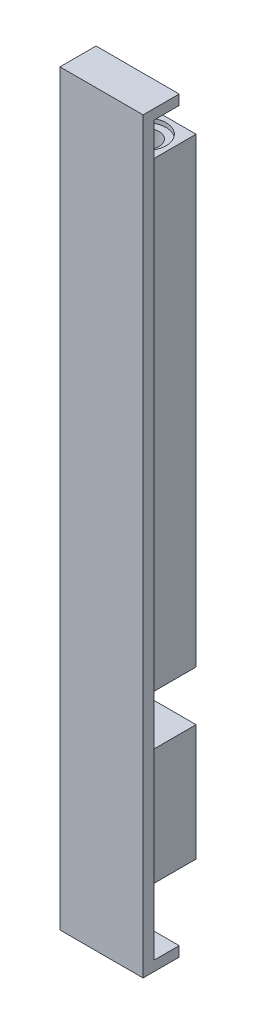
SolidWorks part; units mm, degrees
ref_plane "Front Plane" through (0, 0, 0) normal (0, 0, 1) x (1, 0, 0)
ref_plane "Top Plane" through (0, 0, 0) normal (0, 1, 0) x (1, 0, 0)
ref_plane "Right Plane" through (0, 0, 0) normal (1, 0, 0) x (0, 0, -1)
ref_plane "Plane7" through (0, -5, 0) normal (0, -1, 0) x (-1, 0, 0)
sketch "Sketch1" plane through (0, 0, 0) normal (0, 1, 0) x (1, 0, 0)
  circle A0 centre (0, 0) radius 37.5 construction
  dimension "D1" = 75
sketch "Sketch3" plane through (0, -5, 0) normal (0, -1, 0) x (1, 0, 0)
  line L0 (-3, 37.3798) -> (-3, 31.3798)
  line L1 (-3, 31.3798) -> (3, 31.3798)
  line L2 (3, 31.3798) -> (3, 37.3798)
  line L9 (0, 40.3758) -> (0, -39.6162) construction
  line L10 (0, -55) -> (0, 55) construction
  arc A0 (3, 37.3798) -> (-3, 37.3798) centre (0, 0) ccw
  circle A4 centre (0, 0) radius 37.5 construction
  dimension "D2" = 6
  dimension "D3" = 6
extrude "Boss-Extrude2" add sketch "Sketch3" along normal blind 75.5
sketch "Sketch5" plane through (0, 0, 0) normal (0, 1, 0) x (1, 0, 0)
  line L0 (-5, -38.4094) -> (-5, -39.2364)
  line L1 (5, -38.4094) -> (5, -39.4143)
  line L2 (2, -38.6818) -> (2, -37.4318)
  line L3 (-2, -38.6818) -> (-2, -37.4318)
  line L12 (0, 40.7328) -> (0, -41.0085) construction
  line L13 (0, -4.5877) -> (0, 4.5877) construction
  line L14 (0, -39.7511) -> (-5, -39.7511)
  line L15 (-5, -39.7511) -> (-5, -39.2364)
  line L16 (0, -39.7511) -> (5, -39.7511)
  line L17 (5, -39.7511) -> (5, -39.4143)
  arc A1 (-2, -37.4318) -> (2, -37.4318) centre (0, 0) ccw
  arc A2 (5, -38.4094) -> (2, -38.6818) centre (0, 0) cw
  arc A3 (-5, -38.4094) -> (-2, -38.6818) centre (0, 0) ccw
  circle A13 centre (0, 0) radius 37.5 construction
  dimension "D1" = 4
  dimension "D2" = 10
  dimension "D3" = 1.25
  dimension "D4" = 1.0049
  dimension "D5" = 1.0693
extrude "Boss-Extrude3" add sketch "Sketch5" against normal blind 85.5
sketch "Sketch7" plane through (0, 0, 0) normal (1, 0, 0) x (0, 0, -1)
  line L0 (0, 5.5) -> (0, -5.5) construction
  line L1 (0, -60.5) -> (-37.5, -60.5)
  line L2 (0, -60.5) -> (0, -66.5)
  line L3 (0, -66.5) -> (-37.5, -66.5)
  line L4 (-37.5, -60.5) -> (-37.5, -66.5)
  line L6 (-31.3798, -80.5) -> (-37.3798, -80.5) construction
  line L7 (0, -27.0167) -> (0, -72.0117) construction
  dimension "D1" = 37.5
  dimension "D2" = 6
  dimension "D3" = 14
revolve "Cut-Revolve1" cut sketch "Sketch7" angle 360 about L7
ref_plane "Plane5" through (0, -80.5, 0) normal (0, -1, 0) x (-1, 0, 0)
sketch "Sketch9" plane through (0, -80.5, 0) normal (0, -1, 0) x (-1, 0, 0)
  line L0 (0, -31.1751) -> (0, -37.6667) construction
  line L1 (0, 4.6042) -> (0, -4.6042) construction
  line L2 (-3.1738, -34.4209) -> (3.1592, -34.4209) construction
  circle A0 centre (0, -34.4209) radius 1.55
  dimension "D2" = 3.1
extrude "Cut-Extrude4" cut sketch "Sketch9" against normal blind 4.3
sketch "Sketch10" plane through (0, -80.5, 0) normal (0, -1, 0) x (-1, 0, 0)
  line L0 (0, -31.1751) -> (0, -37.6667) construction
  line L2 (-3.1738, -34.4209) -> (3.1592, -34.4209) construction
  circle A0 centre (0, -34.4209) radius 2.4
  dimension "D2" = 4.8
extrude "Cut-Extrude5" cut sketch "Sketch10" against normal blind 0.5
sketch "Sketch12" plane through (0, -5, 0) normal (0, -1, 0) x (-1, 0, 0)
  circle A0 centre (0, 0) radius 37.5 construction
sketch "Sketch13" plane through (0, -5, 0) normal (0, -1, 0) x (-1, 0, 0)
  line L0 (0, -31.134) -> (0, -37.6256) construction
  line L1 (-2.6479, -34.3798) -> (2.8747, -34.3798) construction
  line L2 (3, -37.3798) -> (3, -31.3798) construction
  line L3 (-3, -31.3798) -> (-3, -37.3798) construction
  circle A0 centre (0, -34.3798) radius 2.4
sketch "Sketch14" plane through (0, -5, 0) normal (0, -1, 0) x (-1, 0, 0)
  line L0 (0, -31.134) -> (0, -37.6256) construction
  line L2 (-3.1738, -34.3798) -> (3.1592, -34.3798) construction
  line L3 (3, -37.3798) -> (3, -31.3798) construction
  line L4 (-3, -31.3798) -> (-3, -37.3798) construction
  circle A0 centre (0, -34.3798) radius 1.55
  dimension "D2" = 3.1
extrude "Cut-Extrude6" cut sketch "Sketch13" along normal blind 0.5
extrude "Cut-Extrude7" cut sketch "Sketch14" along normal blind 4.3
sketch "Skizze1" plane through (0, 0, 0) normal (0, 1, 0) x (1, 0, 0)
  line L0 (-5, -39.7511) -> (5, -39.7511)
  line L1 (5, -39.7511) -> (5, -38.4094)
  line L2 (5, -38.4094) -> (-5, -38.4094)
  line L3 (-5, -38.4094) -> (-5, -39.7511)
extrude "Aufsatz-Linear austragen1" add sketch "Skizze1" along normal blind 2.2
sketch "Skizze2" plane through (0, 0, 38.4094) normal (0, 0, -1) x (-1, 0, 0)
  line L0 (-5, 2.2) -> (-5, 1)
  line L2 (-5, 1) -> (5, 1)
  line L4 (5, 1) -> (5, 2.2)
  line L5 (5, 2.2) -> (-5, 2.2)
  point P3 (0, 0)
  point P5 (0, 0)
  dimension "D1" = 1.2
extrude "Aufsatz-Linear austragen2" add sketch "Skizze2" along normal blind 3
sketch "Skizze3" plane through (0, -85.5, 0) normal (0, -1, 0) x (1, 0, 0)
  line L0 (-5, 39.7511) -> (-5, 38.4094)
  line L1 (-5, 38.4094) -> (5, 38.4094)
  line L2 (5, 38.4094) -> (5, 39.7511)
  line L3 (5, 39.7511) -> (-5, 39.7511)
extrude "Aufsatz-Linear austragen3" add sketch "Skizze3" along normal blind 2.2
sketch "Skizze4" plane through (0, 0, 38.4094) normal (0, 0, -1) x (-1, 0, 0)
  line L0 (-5, -87.7) -> (-5, -86.5)
  line L1 (-5, -87.7) -> (-5, -85.5) construction
  line L2 (-5, -86.5) -> (5, -86.5)
  line L3 (5, -87.7) -> (5, -85.5) construction
  line L4 (5, -86.5) -> (5, -87.7)
  line L5 (5, -87.7) -> (-5, -87.7)
  dimension "D1" = 1.2
extrude "Aufsatz-Linear austragen4" add sketch "Skizze4" along normal blind 3
